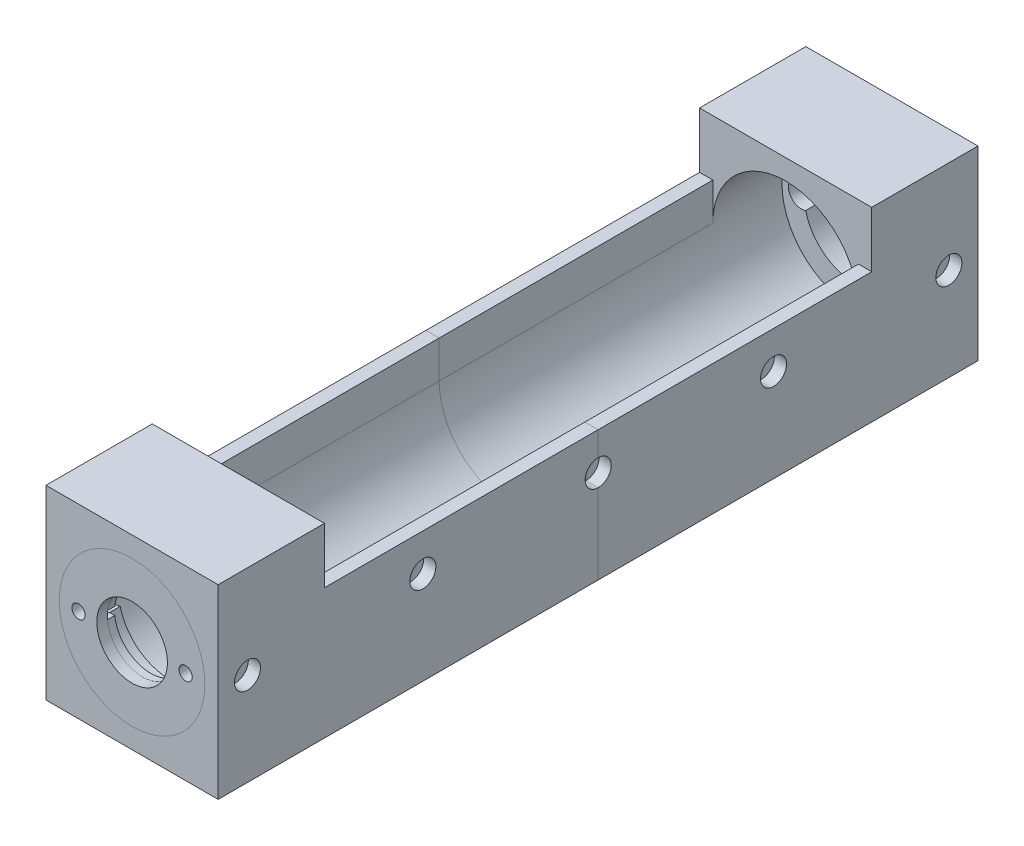
SolidWorks part; units mm, degrees
ref_plane "Alzado" through (0, 0, 0) normal (0, 0, 1) x (1, 0, 0)
ref_plane "Planta" through (0, 0, 0) normal (0, 1, 0) x (1, 0, 0)
ref_plane "Vista lateral" through (0, 0, 0) normal (1, 0, 0) x (0, 0, -1)
sketch "Croquis1" plane through (0, 0, 0) normal (0, 0, 1) x (1, 0, 0)
  line L0 (0, 8.3596) -> (0, -1.3417) construction
  line L1 (9, 0.75) -> (-9, 0.75)
  line L2 (0, 0.75) -> (0, -0.75)
  line L3 (9, -0.75) -> (-9, -0.75)
  line L4 (-9, 0.75) -> (-9, -0.75)
  line L5 (-12.48, 10.7299) -> (-12.48, -4.9079) construction
  line L6 (9, 0.75) -> (9, -0.75)
  line L7 (0, 0) -> (-17.6562, 0) construction
  circle A0 centre (-10.08, 0) radius 2.4
  circle A1 centre (-10.08, 0) radius 0.9
  circle A2 centre (10.08, 0) radius 0.9
  circle A3 centre (10.08, 0) radius 2.4
  circle A4 centre (0, 0) radius 13.7
  point P9 (0, 0)
  dimension "D1" = 1.8
  dimension "D4" = 4.8
  dimension "D6" = 27.4
  dimension "D2" = 1.5
  dimension "D3" = 9
  dimension "D5" = 12.48
extrude "Saliente-Extruir1" add sketch "Croquis1" along normal blind 5 contours A4 L1 A3 L3 A0 region at (-13.3125, 0, 0)
sketch "Croquis2" plane through (0, 0, 5) normal (0, 0, 1) x (1, 0, 0)
  circle A0 centre (0, 0) radius 9.5
  dimension "D1" = 19
extrude "Cortar-Extruir1" cut sketch "Croquis2" against normal blind 3.5
sketch "Croquis3" plane through (0, 0, 1.5) normal (0, 0, 1) x (1, 0, 0)
  circle A0 centre (0, 0) radius 6.8
  dimension "D1" = 13.6
extrude "Cortar-Extruir2" cut sketch "Croquis3" against normal blind 3
sketch "Croquis4" plane through (0, 0, 0) normal (0, 0, -1) x (-1, 0, 0)
  circle A0 centre (0, 0) radius 13.7 construction
  circle A1 centre (0, 0) radius 13.7
  circle A2 centre (0, 0) radius 6.65
  dimension "D1" = 13.3
extrude "Saliente-Extruir2" add sketch "Croquis4" along normal blind 2
sketch "Croquis5" plane through (0, 0, 5) normal (0, 0, 1) x (1, 0, 0)
  circle A0 centre (-10.08, 0) radius 1.25
  circle A1 centre (10.08, 0) radius 1.25
  dimension "D1" = 2.5
  dimension "D2" = 2.5
extrude "Cortar-Extruir3" cut sketch "Croquis5" against normal through all
sketch "Croquis6" plane through (0, 0, -2) normal (0, 0, -1) x (-1, 0, 0)
  line L1 (-16.2, -17.5) -> (16.2, -17.5)
  line L2 (-16.2, -17.5) -> (-16.2, 17.5)
  line L3 (-16.2, 17.5) -> (16.2, 17.5)
  line L4 (16.2, -17.5) -> (16.2, 17.5)
  line L5 (-16.2, -17.5) -> (16.2, 17.5) construction
  line L6 (-16.2, 17.5) -> (16.2, -17.5) construction
  circle A0 centre (0, 0) radius 13.7 construction
  circle A1 centre (0, 0) radius 13.7
  point P0 (0, 0)
  dimension "D1" = 35
  dimension "D2" = 32.4
extrude "Saliente-Extruir3" add sketch "Croquis6" against normal blind 20 separate body
sketch "Croquis8" plane through (0, 0, 18) normal (0, 0, 1) x (1, 0, 0)
  line L0 (-13.7, 0) -> (-13.7, 7)
  line L1 (-13.7, 7) -> (16.2, 7)
  line L2 (13.7, 0) -> (13.7, 7)
  line L3 (13.7, 7) -> (-16.2, 7)
  line L4 (-16.2, 17.5) -> (-16.2, -17.5)
  line L5 (16.2, 17.5) -> (-16.2, 17.5)
  line L6 (16.2, -17.5) -> (16.2, 17.5)
  line L7 (-16.2, -17.5) -> (16.2, -17.5)
  line L8 (-16.2, 17.5) -> (-16.2, 7)
  line L10 (16.2, 7) -> (16.2, 17.5)
  line L11 (-16.2, -17.5) -> (16.2, -17.5)
  line L12 (16.2, 17.5) -> (16.2, -17.5) construction
  line L13 (27.021, 0) -> (-27.7174, 0) construction
  circle A0 centre (0, 0) radius 13.7 construction
  circle A1 centre (0, 0) radius 13.7 construction
  arc A2 (-13.7, 0) -> (13.7, 0) centre (0, 0) ccw
  circle M15 centre (0, 0) radius 13.7
  line M16 (-16.2, 17.5) -> (-16.2, -17.5)
  line M17 (-16.2, -17.5) -> (16.2, -17.5)
  line M18 (16.2, -17.5) -> (16.2, 17.5)
  dimension "D2" = 7
  dimension "D3" = 7
  dimension "D1" = 0
extrude "Saliente-Extruir5" add sketch "Croquis8" along normal blind 51.5 contours L13 M18 M15 M16 M17 | L13 L0 L3 M16 | L13 L1 L2 M18 region at (-14.95, 3.5, 18) region at (0, -14.0682, 18) region at (14.95, 3.5, 18)
ref_plane "Plano1" through (0, 0, 69.5) normal (0, 0, 1) x (1, 0, 0)
mirror "Simetría10" about plane through (0, 0, 69.5) normal (0, 0, 1) of bodies 105 108
sketch "Croquis9" plane through (-16.2, 0, 0) normal (-1, 0, 0) x (0, 0, 1)
  line L0 (0, 0) -> (156.1517, 0) construction
  circle A0 centre (3.4791, 0) radius 2.45
  circle A1 centre (3.4791, 0) radius 16.5 construction
  circle A2 centre (36.4791, 0) radius 16.5 construction
  circle A3 centre (69.4791, 0) radius 16.5 construction
  circle A4 centre (102.4791, 0) radius 16.5 construction
  circle A5 centre (135.4791, 0) radius 16.5 construction
  circle A6 centre (36.4791, 0) radius 2.45
  circle A7 centre (69.4791, 0) radius 2.45
  circle A8 centre (102.4791, 0) radius 2.45
  circle A9 centre (135.4791, 0) radius 2.45
  point P19 (94.9394, 0)
  point P20 (102.4791, 0)
  point P21 (0, 0)
  dimension "D1" = 4.9
  dimension "D3" = 33
  dimension "D2" = 3.4791
extrude "Cortar-Extruir4" cut sketch "Croquis9" against normal blind 2.3
mirror "Simetría11" about plane through (0, 0, 0) normal (1, 0, 0) of "Cortar-Extruir4"
